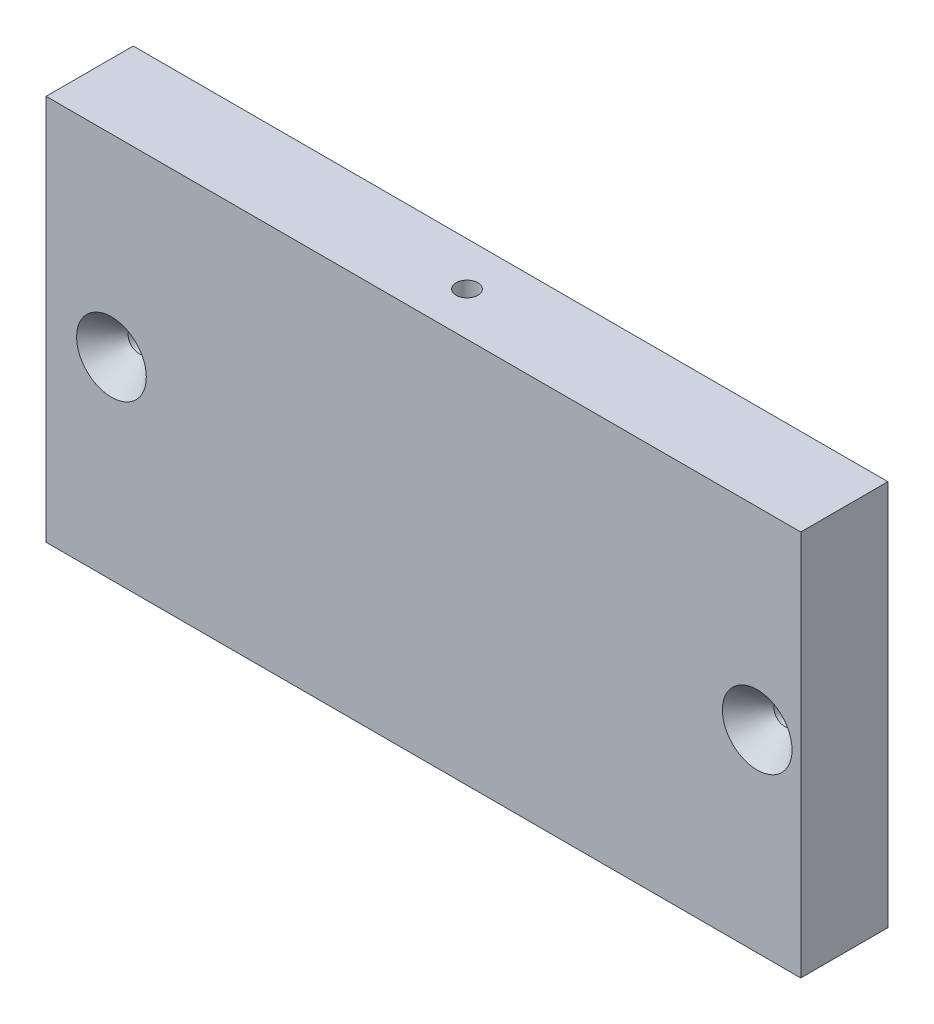
SolidWorks part; units mm, degrees
material "Beech"
ref_plane "Front Plane" through (0, 0, 0) normal (0, 0, 1) x (1, 0, 0)
ref_plane "Top Plane" through (0, 0, 0) normal (0, 1, 0) x (1, 0, 0)
ref_plane "Right Plane" through (0, 0, 0) normal (1, 0, 0) x (0, 0, -1)
sketch "Sketch2" plane through (0, 0, 0) normal (0, 0, 1) x (1, 0, 0)
  line L0 (-231.3045, 12.7) -> (-231.3045, 69)
  line L1 (-341.3045, 12.7) -> (-341.3045, 69)
  line L2 (-341.3045, 69) -> (-231.3045, 69)
  line L7 (-231.3045, 12.7) -> (-341.3045, 12.7)
  dimension "D1" = 56.3
extrude "Boss-Extrude1" add sketch "Sketch2" against normal blind 12.7
hole_wizard "Hole" positions "Sketch4" profile "Sketch5" legacy
sketch "Sketch4" plane through (-124.0045, 277.2867, 0) normal (0, 0, 1) x (-1, 0, 0)
  point P0 (113.65, 236.4367)
  point P2 (207.775, 236.4367)
sketch "Sketch5" plane through (-237.6545, 40.85, 0) normal (1, 0, 0) x (0, -1, 0)
  line L0 (0, 0) -> (0, 32.7039)
  line L1 (0, 32.7039) -> (1.5875, 31.75)
  line L2 (1.5875, 31.75) -> (1.5875, 4.0177)
  line L3 (1.5875, 4.0177) -> (5.08, 0)
  line L4 (5.08, 0) -> (0, 0)
  line L5 (0, -14.3089) -> (0, 102.4216) construction
  line L6 (0, 32.7039) -> (-1.5875, 31.75) construction
  line L7 (-1.5875, 4.0177) -> (-5.08, 0) construction
  dimension "Diameter" = 3.175
  dimension "Depth" = 31.75
  dimension "C-Sink Diameter" = 10.16
  dimension "C-Sink Angle" = 82
  dimension "Drill Angle" = 118
hole_wizard "Hole1" positions "Sketch6" profile "Sketch7" legacy
sketch "Sketch6" plane through (-124.0045, 88.05, -14.9757) normal (0, 1, 0) x (1, 0, 0)
  point P15 (-162.3, -8.6257)
  point P34 (-113.65, 50.1576)
  point P36 (-113.65, 102.591)
  point P54 (162.3, -8.6257)
  point P55 (113.65, 50.1576)
  point P56 (113.65, 102.591)
  point P71 (63.85, 161.3743)
  point P73 (0, 161.3743)
  point P74 (-63.85, 161.3743)
sketch "Sketch7" plane through (-286.3045, 88.05, -6.35) normal (1, 0, 0) x (0, 0, 1)
  line L0 (0, 0) -> (0, 32.7039)
  line L1 (0, 32.7039) -> (1.5875, 31.75)
  line L2 (1.5875, 31.75) -> (1.5875, 4.0177)
  line L3 (1.5875, 4.0177) -> (5.08, 0)
  line L4 (5.08, 0) -> (0, 0)
  line L5 (0, -14.3089) -> (0, 102.4216) construction
  line L6 (0, 32.7039) -> (-1.5875, 31.75) construction
  line L7 (-1.5875, 4.0177) -> (-5.08, 0) construction
  dimension "Diameter" = 3.175
  dimension "Depth" = 31.75
  dimension "C-Sink Diameter" = 10.16
  dimension "C-Sink Angle" = 82
  dimension "Drill Angle" = 118
